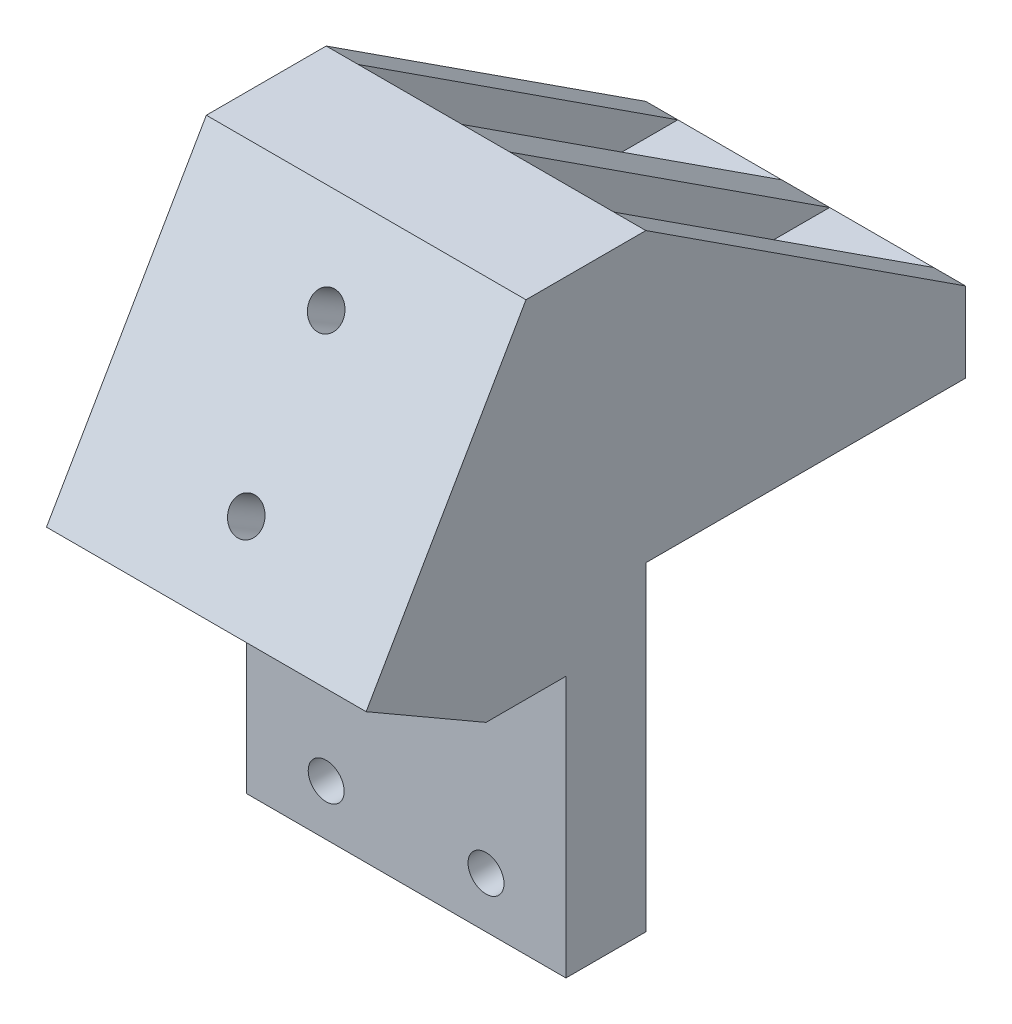
SolidWorks part; units mm, degrees
ref_plane "Plan de face" through (0, 0, 0) normal (0, 0, 1) x (1, 0, 0)
ref_plane "Plan de dessus" through (0, 0, 0) normal (0, 1, 0) x (1, 0, 0)
ref_plane "Plan de droite" through (0, 0, 0) normal (1, 0, 0) x (0, 0, -1)
sketch "Esquisse1" plane through (0, 0, 0) normal (1, 0, 0) x (0, 0, -1)
  line L0 (0, 0) -> (40, 0)
  line L1 (40, 0) -> (40, 10)
  line L2 (40, 10) -> (0, 10)
  line L3 (0, 10) -> (0, 36)
  line L4 (0, 36) -> (-15, 36)
  line L5 (-15, 36) -> (-35, 1.359)
  line L6 (-35, 1.359) -> (-20, -7.3013)
  line L7 (-20, -7.3013) -> (-10, -7.3013)
  line L8 (-10, -7.3013) -> (-10, -40)
  line L9 (-10, -40) -> (0, -40)
  line L10 (0, -40) -> (0, 0)
  point P3 (0, 37.6022)
  point P13 (-19.0235, -4.9783)
  dimension "D1" = 10
  dimension "D2" = 10
  dimension "D3" = 26
  dimension "D4" = 15
  dimension "D5" = 30
  dimension "D6" = 40
  dimension "D7" = 40
  dimension "D8" = 40
  dimension "D9" = 90
  dimension "D10" = 10
extrude "Boss.-Extru.1" add sketch "Esquisse1" along normal blind 40
sketch "Esquisse2" plane through (0, 10, 0) normal (0, 1, 0) x (1, 0, 0)
  line L0 (0, 20) -> (40, 20) construction
  line L1 (0, 40) -> (0, 0) construction
  line L2 (40, 40) -> (40, 0) construction
  line L3 (20, 20) -> (20, 40) construction
  line L4 (40, 40) -> (0, 40) construction
  circle A0 centre (10, 30) radius 2.25
  circle A1 centre (30, 30) radius 2.25
  circle A2 centre (30, 10) radius 2.25
  circle A3 centre (10, 10) radius 2.25
  dimension "D1" = 4.5
  dimension "D2" = 20
  dimension "D3" = 20
extrude "Enlèv. mat.-Extru.1" cut sketch "Esquisse2" against normal through all both and the other way through all
sketch "Esquisse3" plane through (0, 0, 10) normal (0, 0, 1) x (1, 0, 0)
  line L0 (20, -40) -> (20, -23.6506) construction
  line L1 (40, -40) -> (0, -40) construction
  line L2 (20, -23.6506) -> (0, -23.6506) construction
  line L3 (0, -7.3013) -> (0, -40) construction
  circle A0 centre (10, -33.6506) radius 2.25
  circle A1 centre (30, -33.6506) radius 2.25
  circle A2 centre (30, -13.6506) radius 2.25
  circle A3 centre (10, -13.6506) radius 2.25
  dimension "D1" = 20
  dimension "D2" = 20
  dimension "D3" = 4.5
extrude "Enlèv. mat.-Extru.2" cut sketch "Esquisse3" against normal through all both and the other way through all
sketch "Esquisse4" plane through (0, 15.4952, 26.8385) normal (0, 0.5, 0.866) x (1, 0, 0)
  line L0 (20, -16.3231) -> (20, 23.6769) construction
  line L1 (40, -16.3231) -> (0, -16.3231) construction
  line L2 (40, 23.6769) -> (0, 23.6769) construction
  line L3 (20, 3.6769) -> (0, 3.6769) construction
  line L4 (0, 23.6769) -> (0, -16.3231) construction
  circle A0 centre (20, 13.6769) radius 2.1
  circle A1 centre (20, -6.3231) radius 2.1
  dimension "D1" = 4.2
  dimension "D2" = 20
extrude "Enlèv. mat.-Extru.3" cut sketch "Esquisse4" against normal blind 20 and the other way through all
sketch "Esquisse5" plane through (40, 0, 0) normal (1, 0, 0) x (0, 0, -1)
  line L0 (40, 10) -> (0, 36)
  line L1 (0, 36) -> (0, 10)
  line L2 (0, 10) -> (40, 10)
extrude "Boss.-Extru.2" add sketch "Esquisse5" against normal blind 4
extrude "Boss.-Extru.3" add sketch "Esquisse5<2>" along normal blind 4 from surface starting at face at (0, -0.1131, 0.9091)
sketch "Esquisse5<2>" plane through (40, 0, 0) normal (1, 0, 0) x (0, 0, -1) same geometry as "Esquisse5"
extrude "Boss.-Extru.4" add sketch "Esquisse5<3>" along normal blind 3 and the other way blind 3 from offset 20 offset against normal yes
sketch "Esquisse5<3>" plane through (40, 0, 0) normal (1, 0, 0) x (0, 0, -1) same geometry as "Esquisse5"
